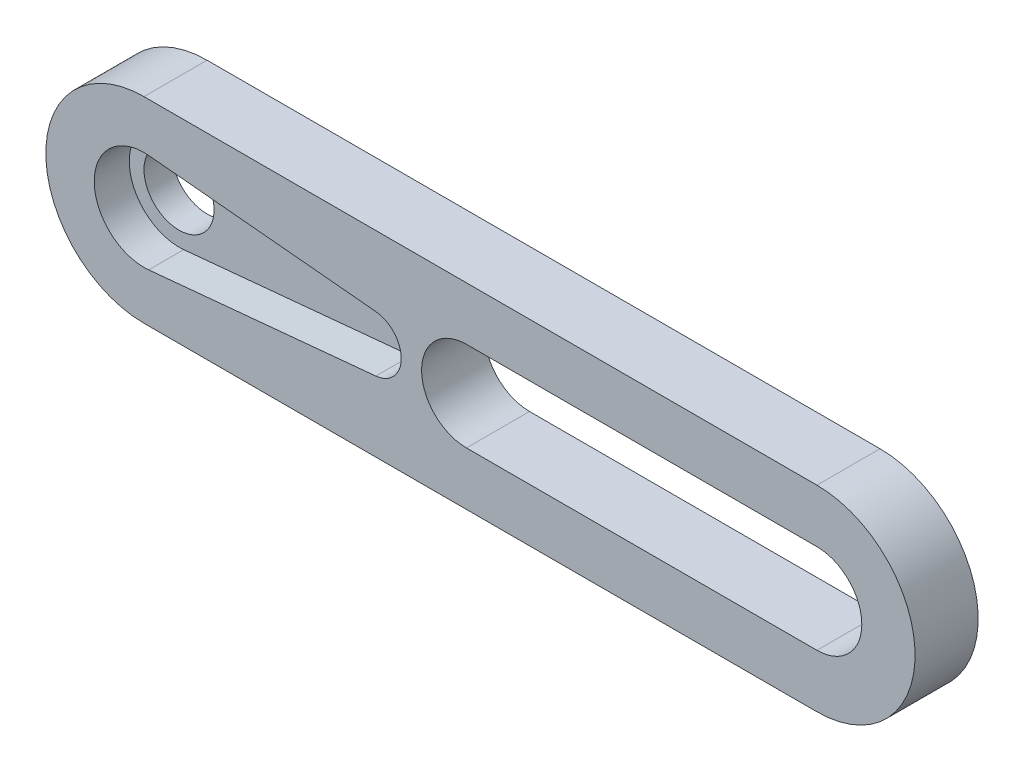
SolidWorks part; units mm, degrees
ref_plane "Front Plane" through (0, 0, 0) normal (0, 0, 1) x (1, 0, 0)
ref_plane "Top Plane" through (0, 0, 0) normal (0, 1, 0) x (1, 0, 0)
ref_plane "Right Plane" through (0, 0, 0) normal (1, 0, 0) x (0, 0, -1)
sketch "Esquisse1" plane through (0, 0, 0) normal (0, 0, 1) x (1, 0, 0)
  line L0 (-3.55, 0) -> (-3.55, 5.3986) construction
  line L1 (0.3365, 3.534) -> (16.5396, 1.991)
  line L2 (16.5396, -1.991) -> (0.3365, -3.534)
  line L3 (18.35, 0) -> (18.35, 4.9554) construction
  line L4 (0, 7) -> (48, 7)
  line L5 (0, -7) -> (48, -7)
  line L6 (23, 0) -> (48, 0) construction
  line L7 (23, 3.2) -> (48, 3.2)
  line L8 (23, -3.2) -> (48, -3.2)
  arc A0 (0.3365, 3.534) -> (0.3365, -3.534) centre (0, 0) ccw
  arc A1 (16.5396, -1.991) -> (16.5396, 1.991) centre (16.35, 0) ccw
  arc A2 (23, 3.2) -> (23, -3.2) centre (23, 0) ccw
  arc A3 (0, -7) -> (0, 7) centre (0, 0) cw
  arc A4 (48, 7) -> (48, -7) centre (48, 0) cw
  arc A5 (48, -3.2) -> (48, 3.2) centre (48, 0) ccw
  point P15 (35.5, 0)
  point P21 (0, 0)
  point P22 (0, 0)
  point P23 (50, -3.534)
  dimension "D2" = 3.55
  dimension "D3" = 2
  dimension "D5" = 25
  dimension "D6" = 7
  dimension "D8" = 7
  dimension "D4" = 3.2
  dimension "D1" = 21.9
  dimension "D7" = 48
extrude "Main" add sketch "Esquisse1" along normal blind 2.5
sketch "Esquisse2" plane through (0, 0, 0) normal (0, 0, -1) x (-1, 0, 0)
  line L0 (0, -7) -> (-48, -7)
  line L1 (0, -7) -> (-48, -7) construction
  line L2 (0, -7) -> (-48, -7) construction
  line L3 (0, 7) -> (-48, 7)
  arc A0 (-48, 7) -> (-48, -7) centre (-48, 0) ccw construction
  circle A2 centre (0, 0) radius 2.5
  arc A3 (0, -7) -> (0, 7) centre (0, 0) ccw
  arc A5 (-48, 7) -> (-48, -7) centre (-48, 0) ccw
  point P2 (-42.1963, -1.7614)
  point P6 (-42.1963, 2.977)
  point P7 (-17.7444, 8)
  point P8 (-16.8859, -8)
  point P11 (-18.9667, 8)
  point P14 (-12.7951, -8)
  point P15 (-48.1993, -8)
  point P21 (-50, 8)
  dimension "D1" = 5
extrude "OriginalBracket" add sketch "Esquisse2" along normal blind 2
sketch "Sketch1" plane through (0, 0, 0) normal (0, 0, 1) x (1, 0, 0)
  line L0 (23, 0) -> (48, 0) construction
  line L1 (23, 3.2) -> (48, 3.2)
  line L2 (23, -3.2) -> (48, -3.2)
  arc A0 (23, 3.2) -> (23, -3.2) centre (23, 0) ccw
  arc A1 (48, -3.2) -> (48, 3.2) centre (48, 0) ccw
  point P4 (35.5, 0)
  point P9 (50, -3.2)
extrude "Cut-Extrude1" cut sketch "Sketch1" against normal through all
